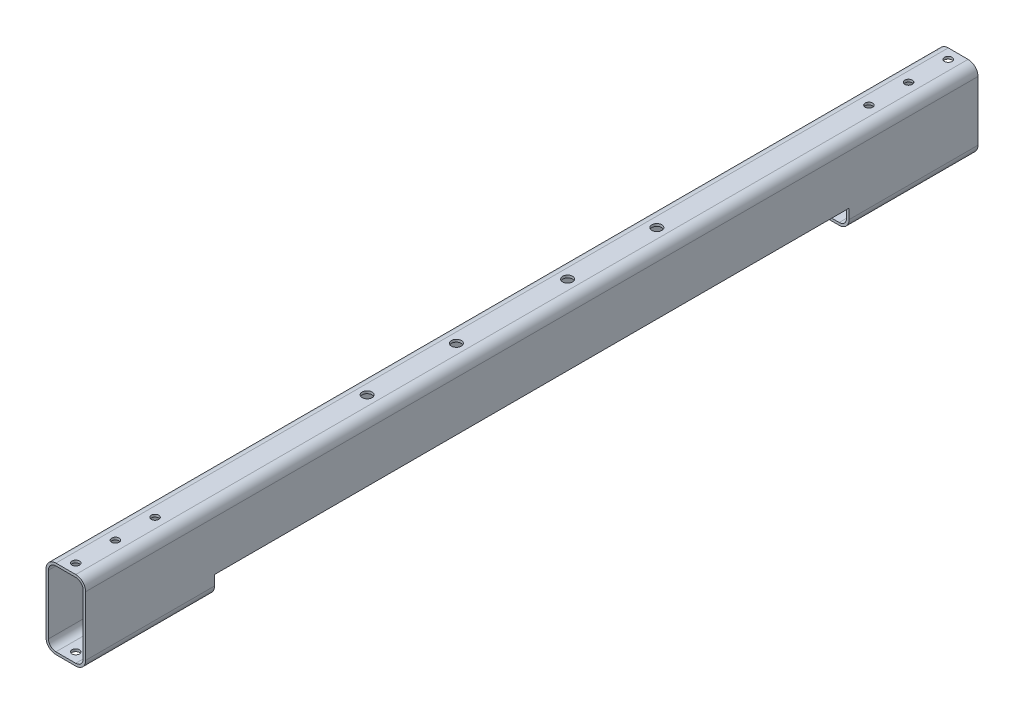
SolidWorks part; units mm, degrees
material "6061-T6 (SS)"
ref_plane "Front Plane" through (0, 0, 0) normal (0, 0, 1) x (1, 0, 0)
ref_plane "Top Plane" through (0, 0, 0) normal (0, 1, 0) x (1, 0, 0)
ref_plane "Right Plane" through (0, 0, 0) normal (1, 0, 0) x (0, 0, -1)
sketch "Sketch1" plane through (0, 0, 0) normal (0, 0, 1) x (1, 0, 0)
  line L1 (-6.35, -25.4) -> (6.35, -25.4)
  line L2 (-12.7, -19.05) -> (-12.7, 19.05)
  line L3 (-6.35, 25.4) -> (6.35, 25.4)
  line L4 (12.7, -19.05) -> (12.7, 19.05)
  line L5 (-12.7, -25.4) -> (12.7, 25.4) construction
  line L6 (-12.7, 25.4) -> (12.7, -25.4) construction
  arc A0 (-12.7, -19.05) -> (-6.35, -25.4) centre (-6.35, -19.05) ccw
  arc A1 (6.35, -25.4) -> (12.7, -19.05) centre (6.35, -19.05) ccw
  arc A2 (6.35, 25.4) -> (12.7, 19.05) centre (6.35, 19.05) cw
  arc A3 (-12.7, 19.05) -> (-6.35, 25.4) centre (-6.35, 19.05) cw
  point P0 (0, 0)
  dimension "D3" = 6.35
  dimension "D1" = 50.8
  dimension "D2" = 25.4
extrude "Extrude-Thin1" add sketch "Sketch1" along normal blind 571.5 thin thin type one direction reverse wall 1.5875
hole_wizard "3/16 (0.1875) Diameter Hole1" positions "3DSketch1" profile "Sketch3" hole size "3/16" standard "ANSI Inch" end condition through all
sketch3d "3DSketch1"
  line L1 (6.35, 25.4, 0) -> (-6.35, 25.4, 0) construction
  line L6 (0, 25.4, 571.5) -> (0, 25.4, 0) construction
  line L7 (6.35, 25.4, 571.5) -> (-6.35, 25.4, 571.5) construction
  point P57 (0, 25.4, 6.35)
  point P59 (0, 25.4, 31.75)
  point P61 (0, 25.4, 57.15)
  point P63 (0, 25.4, 539.75)
  point P65 (0, 25.4, 514.35)
  point P67 (0, 25.4, 565.15)
  dimension "D1" = 25.4
  dimension "D2" = 25.4
  dimension "D3" = 6.35
  dimension "D4" = 25.4
  dimension "D5" = 25.4
  dimension "D6" = 6.35
sketch "Sketch3" plane through (0, 25.4, 565.15) normal (1, 0, 0) x (0, 0, 1)
  line L0 (0, 0) -> (0, 50.8)
  line L1 (0, 50.8) -> (2.3812, 50.8)
  line L2 (2.3812, 50.8) -> (2.3812, 0)
  line L5 (2.3812, 0) -> (0, 0)
  line L11 (0, -6.35) -> (0, 107.95) construction
  dimension "Thru Hole Dia." = 4.7625
  dimension "Thru Hole Depth" = 50.8
sketch "Sketch5" plane through (12.7, 0, 0) normal (1, 0, 0) x (0, 0, -1)
  line L0 (-488.95, -12.7) -> (-488.95, -25.4)
  line L2 (-488.95, -25.4) -> (-82.55, -25.4)
  line L3 (-82.55, -25.4) -> (-82.55, -12.7)
  line L4 (-82.55, -12.7) -> (-488.95, -12.7)
  line L12 (-571.5, -25.4) -> (0, -25.4) construction
  point P11 (-285.75, -25.4)
  point P12 (-285.75, -25.4)
  dimension "D1" = 12.7
  dimension "D2" = 406.4
extrude "Cut-Extrude1" cut sketch "Sketch5" against normal through all
hole_wizard "1/4 (0.25) Diameter Hole1" positions "Sketch6" profile "Sketch7" hole size "1/4" standard "ANSI Inch" end condition through all
sketch "Sketch6" plane through (0, 25.4, 0) normal (0, 1, 0) x (1, 0, 0)
  point P0 (0, -321.3735)
  point P3 (0, -378.5235)
  point P6 (0, -192.9765)
  point P9 (0, -250.1265)
sketch "Sketch7" plane through (0, 25.4, 321.3735) normal (1, 0, 0) x (0, 0, 1)
  line L0 (0, 0) -> (0, 50.8)
  line L1 (0, 50.8) -> (3.175, 50.8)
  line L2 (3.175, 50.8) -> (3.175, 0)
  line L5 (3.175, 0) -> (0, 0)
  line L11 (0, -6.35) -> (0, 107.95) construction
  dimension "Thru Hole Dia." = 6.35
  dimension "Thru Hole Depth" = 50.8
